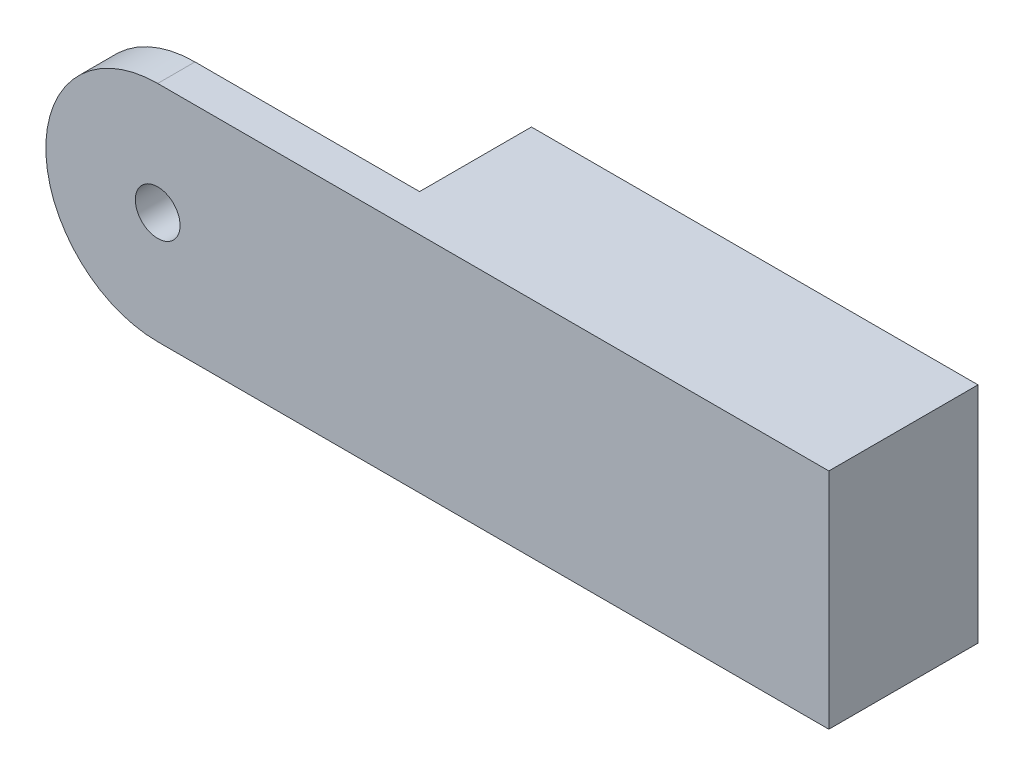
SolidWorks part; units mm, degrees
ref_plane "前视基准面" through (0, 0, 0) normal (0, 0, 1) x (1, 0, 0)
ref_plane "上视基准面" through (0, 0, 0) normal (0, 1, 0) x (1, 0, 0)
ref_plane "右视基准面" through (0, 0, 0) normal (1, 0, 0) x (0, 0, -1)
sketch "草图1" plane through (0, 0, 0) normal (0, 0, 1) x (1, 0, 0)
  line L1 (-45, 15) -> (45, 15)
  line L3 (-45, -15) -> (45, -15)
  line L4 (45, 15) -> (45, -15)
  arc A0 (-45, 15) -> (-45, -15) centre (-45, 0) ccw
  circle A1 centre (-45, 0) radius 3
  point P0 (0, 0)
  dimension "D1" = 30
extrude "凸台-拉伸1" add sketch "草图1" along normal blind 20
ref_plane "基准面1" through (0, 0, 15) normal (0, 0, 1) x (1, 0, 0)
sketch "草图2" plane through (0, 0, 15) normal (0, 0, 1) x (1, 0, 0)
  line L0 (45, 15) -> (-45, 15) construction
  line L1 (-29.6441, 15) -> (-61.6301, 15)
  line L2 (-29.6441, 15) -> (-29.6441, -15)
  line L3 (-29.6441, -15) -> (-61.6301, -15)
  line L4 (-61.6301, 15) -> (-61.6301, -15)
extrude "切除-拉伸2" cut sketch "草图2" against normal through all
sketch "草图3" plane through (0, 0, 15) normal (0, 0, 1) x (1, 0, 0)
  line L0 (45, 15) -> (-29.6441, 15) construction
  line L1 (-14.884, 15) -> (-59.884, 15)
  line L2 (-14.884, 15) -> (-14.884, -15)
  line L3 (-14.884, -15) -> (-59.884, -15)
  line L4 (-59.884, 15) -> (-59.884, -15)
  dimension "D1" = 45
extrude "切除-拉伸3" cut sketch "草图3" against normal through all
